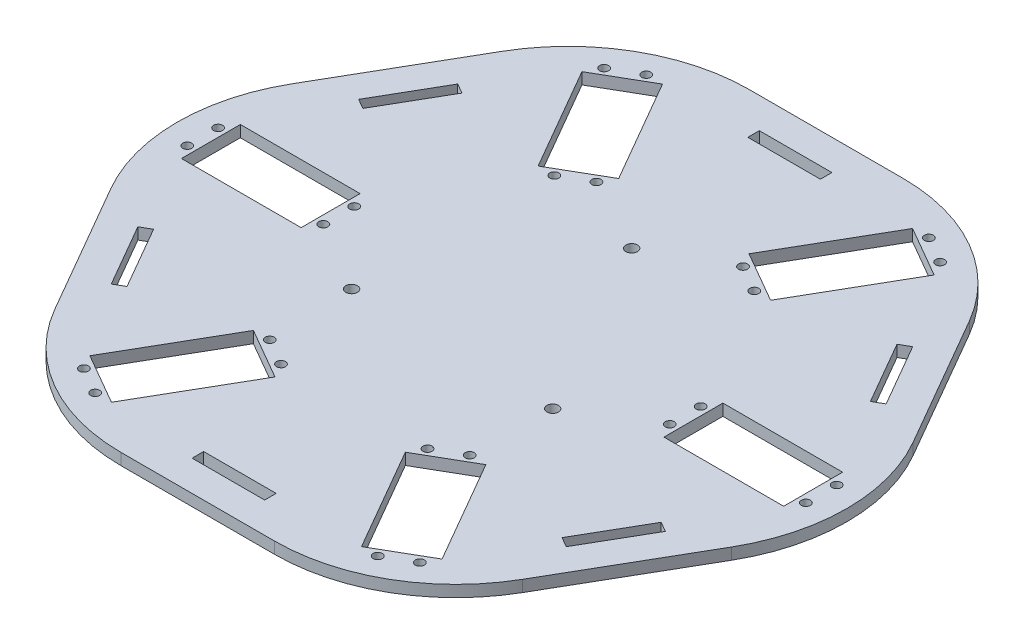
SolidWorks part; units mm, degrees
material "Acrylic (Medium-high impact)"
ref_plane "Front Plane" through (0, 0, 0) normal (0, 0, 1) x (1, 0, 0)
ref_plane "Top Plane" through (0, 0, 0) normal (0, 1, 0) x (1, 0, 0)
ref_plane "Right Plane" through (0, 0, 0) normal (1, 0, 0) x (0, 0, -1)
sketch "Sketch1" plane through (0, 0, 0) normal (0, 1, 0) x (1, 0, 0)
  line L0 (0, 0) -> (200, 0)
  line L1 (171.1325, 50) -> (128.8675, 123.2051)
  line L2 (42.265, 173.2051) -> (-42.265, 173.2051)
  line L3 (-128.8675, 123.2051) -> (-171.1325, 50)
  line L4 (-171.1325, -50) -> (-128.8675, -123.2051)
  line L5 (-42.265, -173.2051) -> (42.265, -173.2051)
  line L6 (128.8675, -123.2051) -> (171.1325, -50)
  line L7 (100, 16.25) -> (166, 16.25)
  line L8 (100, 16.25) -> (100, -16.25)
  line L9 (166, 16.25) -> (166, -16.25)
  line L10 (100, -16.25) -> (166, -16.25)
  line L11 (0, -3.4925) -> (0, 3.4925) construction
  line L12 (-3.4925, 0) -> (3.4925, 0) construction
  line L13 (64.0729, -78.4775) -> (97.0729, -135.6352)
  line L14 (64.0729, -78.4775) -> (35.9271, -94.7275)
  line L15 (35.9271, -94.7275) -> (68.9271, -151.8852)
  line L16 (97.0729, -135.6352) -> (68.9271, -151.8852)
  line L17 (-35.9271, -94.7275) -> (-68.9271, -151.8852)
  line L18 (-35.9271, -94.7275) -> (-64.0729, -78.4775)
  line L19 (-64.0729, -78.4775) -> (-97.0729, -135.6352)
  line L20 (-68.9271, -151.8852) -> (-97.0729, -135.6352)
  line L21 (-100, -16.25) -> (-166, -16.25)
  line L22 (-100, -16.25) -> (-100, 16.25)
  line L23 (-100, 16.25) -> (-166, 16.25)
  line L24 (-166, -16.25) -> (-166, 16.25)
  line L25 (-64.0729, 78.4775) -> (-97.0729, 135.6352)
  line L26 (-64.0729, 78.4775) -> (-35.9271, 94.7275)
  line L27 (-35.9271, 94.7275) -> (-68.9271, 151.8852)
  line L28 (-97.0729, 135.6352) -> (-68.9271, 151.8852)
  line L29 (35.9271, 94.7275) -> (68.9271, 151.8852)
  line L30 (35.9271, 94.7275) -> (64.0729, 78.4775)
  line L31 (64.0729, 78.4775) -> (97.0729, 135.6352)
  line L32 (68.9271, 151.8852) -> (97.0729, 135.6352)
  line L33 (-139.9038, -57.6795) -> (-145.4031, -60.8545)
  line L34 (-20, -150) -> (20, -150)
  line L35 (-20, -150) -> (-20, -156.35)
  line L36 (-20, -156.35) -> (20, -156.35)
  line L37 (20, -150) -> (20, -156.35)
  line L38 (-139.9038, -57.6795) -> (-119.9038, -92.3205)
  line L39 (-119.9038, -92.3205) -> (-125.4031, -95.4955)
  line L40 (-145.4031, -60.8545) -> (-125.4031, -95.4955)
  line L41 (-119.9038, 92.3205) -> (-125.4031, 95.4955)
  line L42 (-119.9038, 92.3205) -> (-139.9038, 57.6795)
  line L43 (-139.9038, 57.6795) -> (-145.4031, 60.8545)
  line L44 (-125.4031, 95.4955) -> (-145.4031, 60.8545)
  line L45 (20, 150) -> (20, 156.35)
  line L46 (20, 150) -> (-20, 150)
  line L47 (-20, 150) -> (-20, 156.35)
  line L48 (20, 156.35) -> (-20, 156.35)
  line L49 (139.9038, 57.6795) -> (145.4031, 60.8545)
  line L50 (139.9038, 57.6795) -> (119.9038, 92.3205)
  line L51 (119.9038, 92.3205) -> (125.4031, 95.4955)
  line L52 (145.4031, 60.8545) -> (125.4031, 95.4955)
  line L53 (119.9038, -92.3205) -> (125.4031, -95.4955)
  line L54 (119.9038, -92.3205) -> (139.9038, -57.6795)
  line L55 (139.9038, -57.6795) -> (145.4031, -60.8545)
  line L56 (125.4031, -95.4955) -> (145.4031, -60.8545)
  line L57 (68.9271, -151.8852) -> (71.9582, -150.1352)
  line L58 (166, 16.25) -> (153, 16.25)
  line L59 (166, 16.25) -> (166, 12.75)
  line L60 (166, 12.75) -> (153, 12.75)
  line L61 (153, 16.25) -> (153, 12.75)
  line L62 (100, -16.25) -> (113, -16.25)
  line L63 (100, -16.25) -> (100, -12.75)
  line L64 (100, -12.75) -> (113, -12.75)
  line L65 (113, -16.25) -> (113, -12.75)
  line L66 (166, -16.25) -> (153, -16.25)
  line L67 (166, -16.25) -> (166, -12.75)
  line L68 (166, -12.75) -> (153, -12.75)
  line L69 (153, -16.25) -> (153, -12.75)
  line L70 (100, 16.25) -> (113, 16.25)
  line L71 (100, 16.25) -> (100, 12.75)
  line L72 (100, 12.75) -> (113, 12.75)
  line L73 (113, 16.25) -> (113, 12.75)
  line L74 (68.9271, -151.8852) -> (62.4271, -140.6269)
  line L75 (62.4271, -140.6269) -> (65.4582, -138.8769)
  line L76 (71.9582, -150.1352) -> (65.4582, -138.8769)
  line L77 (97.0729, -135.6352) -> (94.0418, -137.3852)
  line L78 (97.0729, -135.6352) -> (90.5729, -124.3769)
  line L79 (90.5729, -124.3769) -> (87.5418, -126.1269)
  line L80 (94.0418, -137.3852) -> (87.5418, -126.1269)
  line L81 (64.0729, -78.4775) -> (61.0418, -80.2275)
  line L82 (64.0729, -78.4775) -> (70.5729, -89.7359)
  line L83 (70.5729, -89.7359) -> (67.5418, -91.4859)
  line L84 (61.0418, -80.2275) -> (67.5418, -91.4859)
  line L85 (35.9271, -94.7275) -> (38.9582, -92.9775)
  line L86 (35.9271, -94.7275) -> (42.4271, -105.9859)
  line L87 (42.4271, -105.9859) -> (45.4582, -104.2359)
  line L88 (38.9582, -92.9775) -> (45.4582, -104.2359)
  line L89 (-97.0729, -135.6352) -> (-94.0418, -137.3852)
  line L90 (-97.0729, -135.6352) -> (-90.5729, -124.3769)
  line L91 (-90.5729, -124.3769) -> (-87.5418, -126.1269)
  line L92 (-94.0418, -137.3852) -> (-87.5418, -126.1269)
  line L93 (-68.9271, -151.8852) -> (-71.9582, -150.1352)
  line L94 (-68.9271, -151.8852) -> (-62.4271, -140.6269)
  line L95 (-62.4271, -140.6269) -> (-65.4582, -138.8769)
  line L96 (-71.9582, -150.1352) -> (-65.4582, -138.8769)
  line L97 (-35.9271, -94.7275) -> (-38.9582, -92.9775)
  line L98 (-35.9271, -94.7275) -> (-42.4271, -105.9859)
  line L99 (-42.4271, -105.9859) -> (-45.4582, -104.2359)
  line L100 (-38.9582, -92.9775) -> (-45.4582, -104.2359)
  line L101 (-64.0729, -78.4775) -> (-61.0418, -80.2275)
  line L102 (-64.0729, -78.4775) -> (-70.5729, -89.7359)
  line L103 (-70.5729, -89.7359) -> (-67.5418, -91.4859)
  line L104 (-61.0418, -80.2275) -> (-67.5418, -91.4859)
  line L105 (-166, 16.25) -> (-166, 12.75)
  line L106 (-166, 16.25) -> (-153, 16.25)
  line L107 (-153, 16.25) -> (-153, 12.75)
  line L108 (-166, 12.75) -> (-153, 12.75)
  line L109 (-166, -16.25) -> (-166, -12.75)
  line L110 (-166, -16.25) -> (-153, -16.25)
  line L111 (-153, -16.25) -> (-153, -12.75)
  line L112 (-166, -12.75) -> (-153, -12.75)
  line L113 (-100, -16.25) -> (-100, -12.75)
  line L114 (-100, -16.25) -> (-113, -16.25)
  line L115 (-113, -16.25) -> (-113, -12.75)
  line L116 (-100, -12.75) -> (-113, -12.75)
  line L117 (-100, 16.25) -> (-100, 12.75)
  line L118 (-100, 16.25) -> (-113, 16.25)
  line L119 (-113, 16.25) -> (-113, 12.75)
  line L120 (-100, 12.75) -> (-113, 12.75)
  line L121 (-68.9271, 151.8852) -> (-71.9582, 150.1352)
  line L122 (-68.9271, 151.8852) -> (-62.4271, 140.6269)
  line L123 (-62.4271, 140.6269) -> (-65.4582, 138.8769)
  line L124 (-71.9582, 150.1352) -> (-65.4582, 138.8769)
  line L125 (-97.0729, 135.6352) -> (-94.0418, 137.3852)
  line L126 (-97.0729, 135.6352) -> (-90.5729, 124.3769)
  line L127 (-90.5729, 124.3769) -> (-87.5418, 126.1269)
  line L128 (-94.0418, 137.3852) -> (-87.5418, 126.1269)
  line L129 (-64.0729, 78.4775) -> (-61.0418, 80.2275)
  line L130 (-64.0729, 78.4775) -> (-70.5729, 89.7359)
  line L131 (-70.5729, 89.7359) -> (-67.5418, 91.4859)
  line L132 (-61.0418, 80.2275) -> (-67.5418, 91.4859)
  line L133 (-35.9271, 94.7275) -> (-38.9582, 92.9775)
  line L134 (-35.9271, 94.7275) -> (-42.4271, 105.9859)
  line L135 (-42.4271, 105.9859) -> (-45.4582, 104.2359)
  line L136 (-38.9582, 92.9775) -> (-45.4582, 104.2359)
  line L137 (97.0729, 135.6352) -> (94.0418, 137.3852)
  line L138 (97.0729, 135.6352) -> (90.5729, 124.3769)
  line L139 (90.5729, 124.3769) -> (87.5418, 126.1269)
  line L140 (94.0418, 137.3852) -> (87.5418, 126.1269)
  line L141 (68.9271, 151.8852) -> (71.9582, 150.1352)
  line L142 (68.9271, 151.8852) -> (62.4271, 140.6269)
  line L143 (62.4271, 140.6269) -> (65.4582, 138.8769)
  line L144 (71.9582, 150.1352) -> (65.4582, 138.8769)
  line L145 (35.9271, 94.7275) -> (38.9582, 92.9775)
  line L146 (35.9271, 94.7275) -> (42.4271, 105.9859)
  line L147 (42.4271, 105.9859) -> (45.4582, 104.2359)
  line L148 (38.9582, 92.9775) -> (45.4582, 104.2359)
  line L149 (64.0729, 78.4775) -> (61.0418, 80.2275)
  line L150 (64.0729, 78.4775) -> (70.5729, 89.7359)
  line L151 (70.5729, 89.7359) -> (67.5418, 91.4859)
  line L152 (61.0418, 80.2275) -> (67.5418, 91.4859)
  circle A0 centre (0, 0) radius 200 construction
  circle A5 centre (40.3888, -86.9554) radius 2.5
  circle A6 centre (55.1112, -78.4554) radius 2.5
  circle A7 centre (92.6112, -143.4073) radius 2.5
  circle A8 centre (77.8888, -151.9073) radius 2.5
  circle A9 centre (-55.1112, -78.4554) radius 2.5
  circle A10 centre (-40.3888, -86.9554) radius 2.5
  circle A11 centre (-77.8888, -151.9073) radius 2.5
  circle A12 centre (-92.6112, -143.4073) radius 2.5
  circle A13 centre (-95.5, 8.5) radius 2.5
  circle A14 centre (-95.5, -8.5) radius 2.5
  circle A15 centre (-170.5, -8.5) radius 2.5
  circle A16 centre (-170.5, 8.5) radius 2.5
  circle A17 centre (-40.3888, 86.9554) radius 2.5
  circle A18 centre (-55.1112, 78.4554) radius 2.5
  circle A19 centre (-92.6112, 143.4073) radius 2.5
  circle A20 centre (-77.8888, 151.9073) radius 2.5
  circle A21 centre (55.1112, 78.4554) radius 2.5
  circle A22 centre (40.3888, 86.9554) radius 2.5
  circle A23 centre (77.8888, 151.9073) radius 2.5
  circle A24 centre (92.6112, 143.4073) radius 2.5
  arc A25 (-42.265, 173.2051) -> (-128.8675, 123.2051) centre (-42.265, 73.2051) ccw
  arc A26 (-171.1325, 50) -> (-171.1325, -50) centre (-84.5299, 0) ccw
  arc A27 (-128.8675, -123.2051) -> (-42.265, -173.2051) centre (-42.265, -73.2051) ccw
  arc A28 (42.265, -173.2051) -> (128.8675, -123.2051) centre (42.265, -73.2051) ccw
  arc A29 (171.1325, -50) -> (171.1325, 50) centre (84.5299, 0) ccw
  arc A30 (128.8675, 123.2051) -> (42.265, 173.2051) centre (42.265, 73.2051) ccw
  circle A31 centre (95.5, 8.5) radius 2.5
  circle A32 centre (95.5, -8.5) radius 2.5
  circle A33 centre (170.5, -8.5) radius 2.5
  circle A34 centre (170.5, 8.5) radius 2.5
  point P88 (0, 0)
  point P94 (100, -173.2051)
  point P102 (0, 0)
  point P128 (0, 0)
  point P220 (0, 0)
  dimension "D1" = 400
  dimension "D7" = 2
  dimension "D8" = 40
  dimension "D9" = 20
  dimension "D10" = 6.35
  dimension "D20" = 100
  dimension "D2" = 200
  dimension "D3" = 66
  dimension "D4" = 32.5
  dimension "D5" = 100
  dimension "D6" = 16.25
  dimension "D11" = 150
  dimension "D12" = 6
  dimension "D13" = 13
  dimension "D14" = 3.5
  dimension "D15" = 13
  dimension "D16" = 3.5
  dimension "D17" = 6
  dimension "D19" = 6
extrude "Boss-Extrude1" add sketch "Sketch1" along normal blind 6.35 contours L10 L8 L7 L9 L1 L2 L3 L4 L5 L6 A24 A23 A22 A21 A20 A19 A18 A17 A16 A15 A14 A13 A12 A11 A10 A9 A8 region at (176.2333, 0, 24.5718)
sketch "Sketch2" plane through (0, 6.35, 0) normal (0, 1, 0) x (1, 0, 0)
  line L0 (0, -1.1339) -> (85.0289, -1.1339)
  line L1 (0, -3.4925) -> (0, 3.4925) construction
  line L2 (55.7942, -33.3467) -> (0, -1.1339)
  circle A0 centre (55.7942, -33.3467) radius 3.2
  circle A1 centre (-56.7762, -31.6459) radius 3.2
  circle A2 centre (0.982, 64.9926) radius 3.2
  point P14 (0, 0)
  dimension "D3" = 6.4
  dimension "D1" = 65
  dimension "D2" = 30
  dimension "D4" = 3
extrude "Cut-Extrude1" cut sketch "Sketch2" against normal up to surface (6.35 mm away) contours A2 | A0 | A1 up to face at (0, 0, 0)
